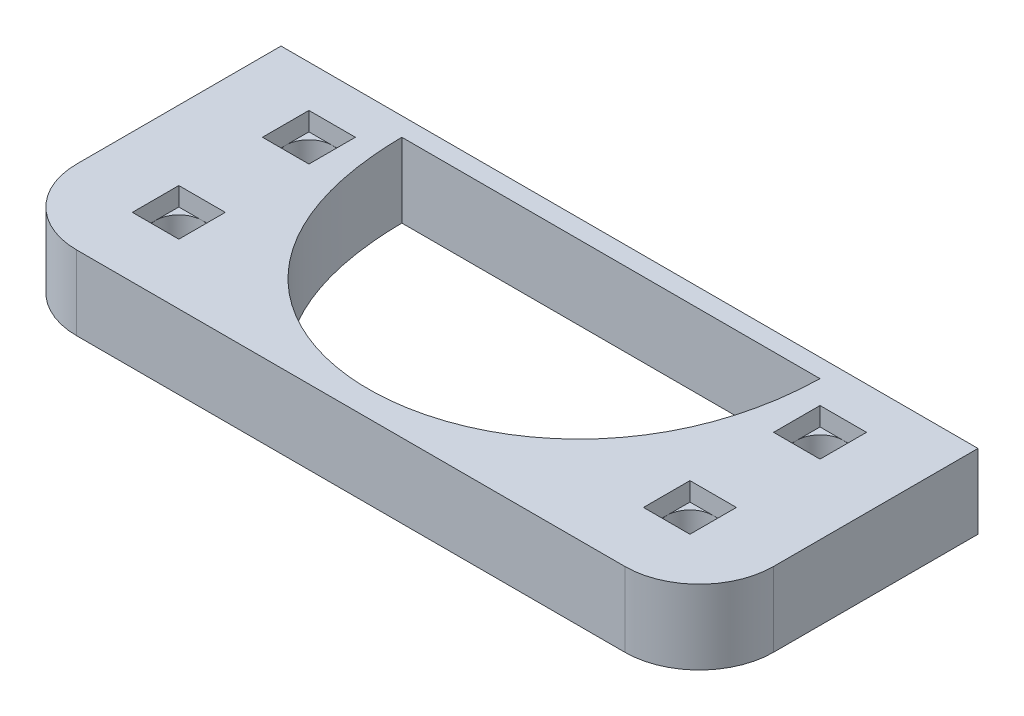
SolidWorks part; units mm, degrees
ref_plane "Front Plane" through (0, 0, 0) normal (0, 0, 1) x (1, 0, 0)
ref_plane "Top Plane" through (0, 0, 0) normal (0, 1, 0) x (1, 0, 0)
ref_plane "Right Plane" through (0, 0, 0) normal (1, 0, 0) x (0, 0, -1)
sketch "Sketch1" plane through (0, 0, 0) normal (0, 1, 0) x (1, 0, 0)
  line L1 (0, 0) -> (75, 0)
  line L2 (0, 0) -> (0, 30)
  line L3 (0, 30) -> (75, 30)
  line L4 (75, 0) -> (75, 30)
  dimension "D1" = 75
  dimension "D2" = 30
extrude "Boss-Extrude1" add sketch "Sketch1" along normal blind 8
sketch "Sketch2" plane through (0, 8, 0) normal (0, 1, 0) x (1, 0, 0)
  line L0 (15, 28) -> (60, 28)
  line L1 (0, 30) -> (0, 0) construction
  line L2 (75, 30) -> (0, 30) construction
  line L3 (75, 0) -> (75, 30) construction
  line L5 (12.5, 25.5) -> (7.5, 25.5)
  line L6 (12.5, 25.5) -> (12.5, 20.5)
  line L7 (12.5, 20.5) -> (7.5, 20.5)
  line L8 (7.5, 25.5) -> (7.5, 20.5)
  line L9 (12.5, 25.5) -> (7.5, 20.5) construction
  line L10 (12.5, 20.5) -> (7.5, 25.5) construction
  line L11 (12.5, 11.5) -> (7.5, 11.5)
  line L12 (12.5, 11.5) -> (12.5, 6.5)
  line L13 (12.5, 6.5) -> (7.5, 6.5)
  line L14 (7.5, 11.5) -> (7.5, 6.5)
  line L15 (12.5, 11.5) -> (7.5, 6.5) construction
  line L16 (12.5, 6.5) -> (7.5, 11.5) construction
  line L17 (62.5, 11.5) -> (67.5, 11.5)
  line L18 (62.5, 11.5) -> (62.5, 6.5)
  line L19 (62.5, 6.5) -> (67.5, 6.5)
  line L20 (67.5, 11.5) -> (67.5, 6.5)
  line L21 (62.5, 11.5) -> (67.5, 6.5) construction
  line L22 (62.5, 6.5) -> (67.5, 11.5) construction
  line L23 (62.5, 25.5) -> (67.5, 25.5)
  line L24 (62.5, 25.5) -> (62.5, 20.5)
  line L25 (62.5, 20.5) -> (67.5, 20.5)
  line L26 (67.5, 25.5) -> (67.5, 20.5)
  line L27 (62.5, 25.5) -> (67.5, 20.5) construction
  line L28 (62.5, 20.5) -> (67.5, 25.5) construction
  circle A0 centre (10, 23) radius 2.5
  circle A1 centre (10, 9) radius 2.5
  circle A2 centre (65, 23) radius 2.5
  circle A3 centre (65, 9) radius 2.5
  spline S0 degree 3 poles (60, 28) (59.2636, -4.3321) (15.3361, -7.0196) (15, 28) knots 0 0 0 0 1 1 1 1
  dimension "D3" = 2
  dimension "D5" = 5
  dimension "D6" = 5
  dimension "D7" = 5
  dimension "D8" = 5
  dimension "D1" = 45
  dimension "D2" = 15
  dimension "D4" = 14
  dimension "D9" = 10
  dimension "D10" = 10
  dimension "D11" = 7
  dimension "D12" = 5
  dimension "D13" = 5
  dimension "D14" = 5
  dimension "D15" = 5
  dimension "D16" = 5
  dimension "D17" = 5
  dimension "D18" = 5
  dimension "D19" = 5
extrude "Cut-Extrude1" cut sketch "Sketch2" against normal through all contours A0 | A1 | A3 | A2 | S0 L0
extrude "Cut-Extrude2" cut sketch "Sketch2<3>" against normal blind 2 contours A1 L13 L12 | A1 L12 L11 | A1 L11 L14 | A1 L14 L13 | A0 L5 L8 | A0 L6 L5 | A0 L7 L6 | A0 L8 L7 | A2 L23 L24 | A2 L26 L23 | A2 L25 L26 | A2 L24 L25 | A3 L19 L20 | A3 L18 L19 | A3 L17 L18 | A3 L20 L17 region at (11.9416, 8, -24.9416) region at (8.0584, 8, -24.9416) region at (11.9416, 8, -21.0584) region at (8.0584, 8, -21.0584) region at (11.9416, 8, -10.9416) region at (8.0584, 8, -10.9416) region at (11.9416, 8, -7.0584) region at (8.0584, 8, -7.0584) region at (63.0584, 8, -10.9416) region at (66.9416, 8, -10.9416) region at (63.0584, 8, -7.0584) region at (66.9416, 8, -7.0584) region at (63.0584, 8, -24.9416) region at (66.9416, 8, -24.9416) region at (63.0584, 8, -21.0584) region at (66.9416, 8, -21.0584)
sketch "Sketch2<3>" plane through (0, 8, 0) normal (0, 1, 0) x (1, 0, 0) same geometry as "Sketch2"
fillet "Fillet1" radius 8 2 edges at (75, 4, 0) (0, 4, 0)
sketch "Sketch3" plane through (0, 0, -30) normal (0, 0, -1) x (-1, 0, 0)
  line L0 (-75, 8) -> (0, 8) construction
  line L1 (0, 8) -> (0, 0) construction
  line L2 (-75, 8) -> (-75, 0) construction
  circle A0 centre (-4, 4) radius 1.75
  circle A1 centre (-71, 4) radius 1.75
  point P6 (0, 0)
  dimension "D2" = 3.5
  dimension "D3" = 3.5
  dimension "D1" = 4
  dimension "D4" = 4
  dimension "D5" = 4
extrude "Cut-Extrude3" cut sketch "Sketch3" against normal blind 25
